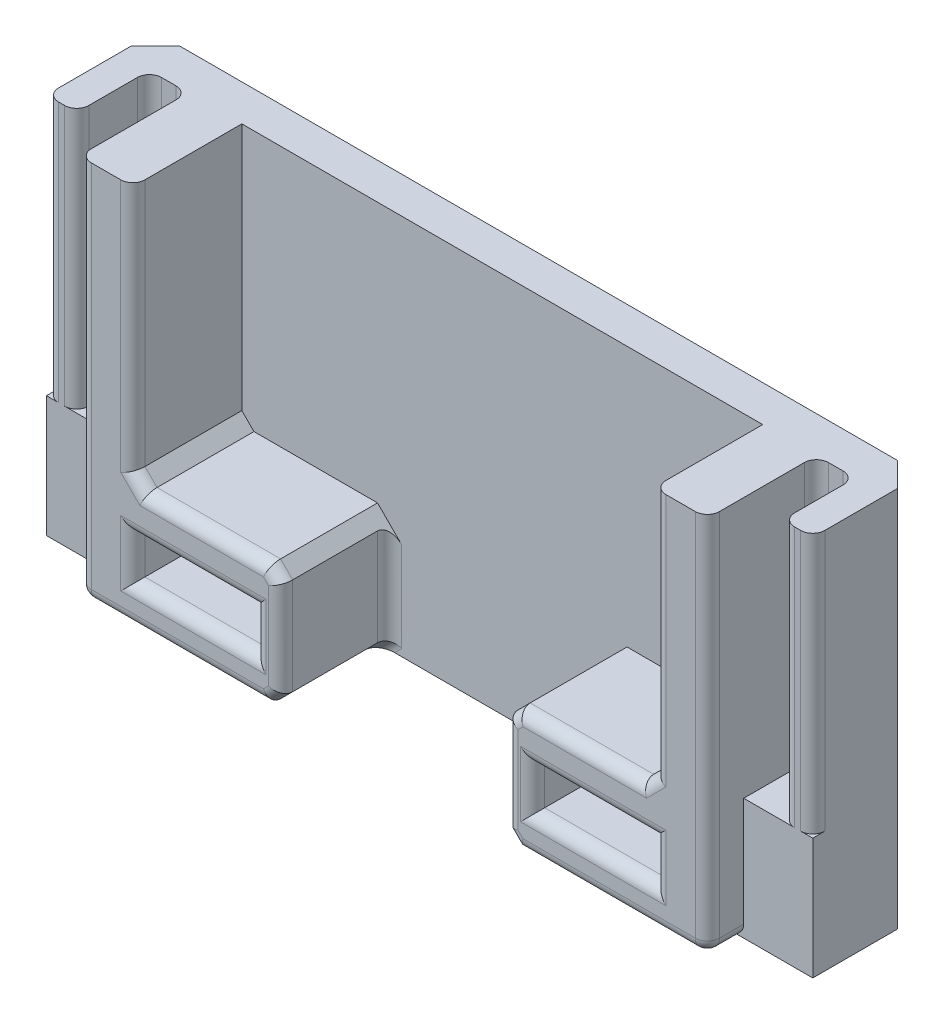
SolidWorks part; units mm, degrees
ref_plane "Plan de face" through (0, 0, 0) normal (0, 0, 1) x (1, 0, 0)
ref_plane "Plan de dessus" through (0, 0, 0) normal (0, 1, 0) x (1, 0, 0)
ref_plane "Plan de droite" through (0, 0, 0) normal (1, 0, 0) x (0, 0, -1)
sketch "Esquisse2" plane through (0, 0, 0) normal (0, 0, 1) x (1, 0, 0)
  line L0 (0, -21.5) -> (0, -31.5)
  line L1 (-21.5, -21.5) -> (21.5, -21.5)
  line L2 (-21.5, -21.5) -> (-21.5, 21.5)
  line L3 (-21.5, 21.5) -> (21.5, 21.5)
  line L4 (21.5, -21.5) -> (21.5, 21.5)
  line L5 (-21.5, -21.5) -> (21.5, 21.5) construction
  line L6 (-21.5, 21.5) -> (21.5, -21.5) construction
  line L7 (-25.9306, -31.5) -> (25.9306, -31.5)
  line L8 (-25.9306, -31.5) -> (-25.9306, 31.5)
  line L9 (-25.9306, 31.5) -> (25.9306, 31.5)
  line L10 (25.9306, -31.5) -> (25.9306, 31.5)
  line L11 (-25.9306, -31.5) -> (25.9306, 31.5) construction
  line L12 (-25.9306, 31.5) -> (25.9306, -31.5) construction
  line L13 (9.3, -21.5) -> (9.3, -31.5)
  line L14 (9.3, -21.5) -> (-9.3, -21.5)
  line L15 (0, -21.5) -> (0, -31.5)
  line L16 (9.3, -31.5) -> (-9.3, -31.5)
  line L17 (-9.3, -21.5) -> (-9.3, -31.5)
  point P0 (0, 0)
  point P6 (0, 0)
  dimension "D1" = 43
  dimension "D2" = 43
  dimension "D3" = 10
  dimension "D4" = 9.3
extrude "Boss.-Extru.2" add sketch "Esquisse2" along normal blind 9 contours L17 L1 L2 L3 L4 L13 L7 L10 L9 L8 region at (-10.116, -26.5, 0)
sketch "Esquisse3" plane through (0, 0, 0) normal (0, 0, -1) x (-1, 0, 0)
  line L1 (-25.9306, 31.5) -> (25.9306, 31.5)
  line L2 (-25.9306, 31.5) -> (-25.9306, -31.5)
  line L3 (-25.9306, -31.5) -> (25.9306, -31.5)
  line L4 (25.9306, 31.5) -> (25.9306, -31.5)
extrude "Boss.-Extru.3" add sketch "Esquisse3" along normal blind 3
sketch "Esquisse4" plane through (0, 0, 9) normal (0, 0, 1) x (1, 0, 0)
  line L0 (0, 31.5) -> (0, -31.5)
  line L1 (-25.9306, 31.5) -> (25.9306, 31.5) construction
  line L2 (9.3, -31.5) -> (-9.3, -31.5) construction
  line L3 (-21.5, 21.5) -> (-21.5, 28.3955)
  line L4 (-25.9306, 0) -> (0, 0)
  line L5 (-21.5, 28.3955) -> (-11.5, 28.3955)
  line L6 (-21.5, 28.3955) -> (-21.5, 24.9955)
  line L7 (-21.5, 24.9955) -> (-11.5, 24.9955)
  line L8 (-11.5, 28.3955) -> (-11.5, 24.9955)
  line L9 (-25.9306, -31.5) -> (-25.9306, 31.5) construction
  line L10 (-21.5, -24.9955) -> (-11.5, -24.9955)
  line L11 (-11.5, -28.3955) -> (-11.5, -24.9955)
  line L12 (-21.5, -28.3955) -> (-11.5, -28.3955)
  line L13 (-21.5, -28.3955) -> (-21.5, -24.9955)
  line L14 (21.5, -28.3955) -> (21.5, -24.9955)
  line L15 (21.5, -28.3955) -> (11.5, -28.3955)
  line L16 (11.5, -28.3955) -> (11.5, -24.9955)
  line L17 (21.5, -24.9955) -> (11.5, -24.9955)
  line L18 (21.5, 24.9955) -> (11.5, 24.9955)
  line L19 (11.5, 28.3955) -> (11.5, 24.9955)
  line L20 (21.5, 28.3955) -> (11.5, 28.3955)
  line L21 (21.5, 28.3955) -> (21.5, 24.9955)
  dimension "D1" = 3.4
extrude "Enlèv. mat.-Extru.1" cut sketch "Esquisse4" against normal blind 7 contours L13 L12 L11 L10 | L14 L17 L16 L15 | L18 L19 L20 L21 | L6 L7 L8 L5 region at (-16.5, -26.6955, 9) region at (16.5, -26.6955, 9)
sketch "Esquisse5" plane through (0, 31.5, 0) normal (0, 1, 0) x (1, 0, 0)
  line L0 (0, 3) -> (0, -9)
  line L1 (-25.9306, 3) -> (25.9306, 3) construction
  line L2 (-25.9306, -9) -> (25.9306, -9) construction
  line L3 (25.9306, 0) -> (29.1306, 0)
  line L4 (-25.9306, 3) -> (-29.1306, 3)
  line L5 (-25.9306, 3) -> (-25.9306, 0)
  line L6 (-25.9306, 0) -> (-29.1306, 0)
  line L7 (-29.1306, 3) -> (-29.1306, 0)
  line L8 (-29.1306, 3) -> (-31.6306, 3)
  line L9 (-29.1306, 3) -> (-29.1306, -6)
  line L10 (-29.1306, -6) -> (-31.6306, -6)
  line L11 (-31.6306, 3) -> (-31.6306, -6)
  line L12 (29.1306, 3) -> (29.1306, 0)
  line L13 (25.9306, 3) -> (29.1306, 3)
  line L14 (25.9306, 3) -> (25.9306, 0)
  line L15 (29.1306, -6) -> (31.6306, -6)
  line L16 (31.6306, 3) -> (31.6306, -6)
  line L17 (29.1306, 3) -> (31.6306, 3)
  line L18 (29.1306, 3) -> (29.1306, -6)
  line M10 (25.9306, -9) -> (25.9306, 3)
  line M12 (-25.9306, 3) -> (-25.9306, -9)
  dimension "D1" = 9
  dimension "D2" = 2.5
  dimension "D3" = 3.2
extrude "Boss.-Extru.4" add sketch "Esquisse5" against normal up to surface (63 mm away) contours L8 L11 L10 L9 L7 | L4 L7 L6 M12 | L13 L3 L12 M10 | L12 L18 L15 L16 L17 region at (27.5306, 31.5, -1.5) region at (30.3806, 31.5, 1.5) region at (-27.5306, 31.5, -1.5) region at (-30.3806, 31.5, 1.5) up to face at (0, -31.5, 3.75)
chamfer "Chanfrein1" distance 1 angle 45 4 edges at (-21.5, -21.5, 4.5) (21.5, -21.5, 4.5) (21.5, 21.5, 4.5) (-21.5, 21.5, 4.5)
chamfer "Chanfrein2" distance 2 angle 45 4 edges at (-31.6306, 0, -3) (0, -31.5, -3) (31.6306, 0, -3) (0, 31.5, -3)
fillet "Congé1" radius 1 8 edges at (31.6306, 0, 6) (29.1306, 0, 6) (29.1306, 0, 0) (25.9306, 0, 0) (-29.1306, 0, 6) (-31.6306, 0, 6) (-29.1306, 0, 0) (-25.9306, 0, 0)
fillet "Congé2" radius 1 36 edges at (-31.6306, 31.5, 2) (-31.3377, 31.5, 5.7071) (-30.3806, 31.5, 6) (-29.4235, 31.5, 5.7071) (-29.1306, 31.5, 3) (-28.8377, 31.5, 0.2929) (-27.5306, 31.5, 0) (-26.2235, 31.5, 0.2929) (-31.6306, -31.5, 2) (-31.3377, -31.5, 5.7071) (-30.3806, -31.5, 6) (-29.4235, -31.5, 5.7071) (-29.1306, -31.5, 3) (-28.8377, -31.5, 0.2929) (-27.5306, -31.5, 0) (-26.2235, -31.5, 0.2929) (31.6306, -31.5, 2) (31.3377, -31.5, 5.7071) (30.3806, -31.5, 6) (29.4235, -31.5, 5.7071) (29.1306, -31.5, 3) (28.8377, -31.5, 0.2929) (27.5306, -31.5, 0) (26.2235, -31.5, 0.2929) (31.6306, 31.5, 2) (31.3377, 31.5, 5.7071) (30.3806, 31.5, 6) (29.4235, 31.5, 5.7071) (29.1306, 31.5, 3) (28.8377, 31.5, 0.2929) (27.5306, 31.5, 0) (26.2235, 31.5, 0.2929) (-25.9306, 31.5, 5) (-25.9306, -31.5, 5) (25.9306, -31.5, 5) (25.9306, 31.5, 5)
chamfer "Chanfrein4" distance 1 angle 45 4 edges at (9.3, -31.5, 4.5) (-9.3, -31.5, 4.5) (9.3, -21.5, 4.5) (-9.3, -21.5, 4.5)
fillet "Congé4" radius 1 40 edges at (-16.5, 24.9955, 9) (-11.5, 26.6955, 9) (-16.5, 28.3955, 9) (-21.5, 26.6955, 9) (11.5, 26.6955, 9) (16.5, 24.9955, 9) (21.5, 26.6955, 9) (16.5, 28.3955, 9) (-11.5, -26.6955, 9) (-16.5, -24.9955, 9) (-21.5, -26.6955, 9) (-16.5, -28.3955, 9) (9.8, -22, 9) (15.4, -21.5, 9) (21, -21, 9) (21.5, 0, 9) (21, 21, 9) (0, 21.5, 9) (-21, 21, 9) (-21.5, 0, 9) (-21, -21, 9) (-15.4, -21.5, 9) (-9.8, -22, 9) (-9.3, -26.5, 9) (-9.8, -31, 9) (-17.6153, -31.5, 9) (-25.6377, -31.2071, 9) (-25.9306, 0, 9) (-25.6377, 31.2071, 9) (0, 31.5, 9) (25.6377, 31.2071, 9) (25.9306, 0, 9) (25.6377, -31.2071, 9) (17.6153, -31.5, 9) (9.8, -31, 9) (9.3, -26.5, 9) (16.5, -24.9955, 9) (11.5, -26.6955, 9) (16.5, -28.3955, 9) (21.5, -26.6955, 9)
fillet "Congé5" radius 1 4 edges at (9.8, -31, 0) (9.3, -26.5, 0) (-9.8, -31, 0) (-9.3, -26.5, 0)
sketch "Esquisse6" plane through (0, -31.5, 0) normal (0, -1, 0) x (1, 0, 0)
  line L0 (-26.9306, -1) -> (26.9306, -1) construction
  line L1 (31.6306, 5) -> (24.9271, 5)
  line L2 (31.6306, 5) -> (31.6306, -1)
  line L3 (31.6306, -1) -> (24.9271, -1)
  line L4 (24.9271, 5) -> (24.9271, -1)
  line L5 (0, -1) -> (0, 5)
  line L6 (24.9271, 5) -> (31.6306, 5)
  line L7 (24.9271, 5) -> (24.9271, 6)
  line L8 (24.9271, 6) -> (31.6306, 6)
  line L9 (31.6306, 5) -> (31.6306, 6)
  line L10 (-24.9271, 6) -> (-31.6306, 6)
  line L11 (-31.6306, 5) -> (-31.6306, 6)
  line L12 (-24.9271, 5) -> (-31.6306, 5)
  line L13 (-24.9271, 5) -> (-24.9271, 6)
  line L14 (-31.6306, -1) -> (-24.9271, -1)
  line L15 (-24.9271, 5) -> (-24.9271, -1)
  line L16 (-31.6306, 5) -> (-24.9271, 5)
  line L17 (-31.6306, 5) -> (-31.6306, -1)
  line M14 (-24.9306, 8) -> (-24.9306, 1)
  arc M15 (-24.9306, 1) -> (-26.9306, -1) centre (-26.9306, 1) cw
  arc M17 (26.9306, -1) -> (24.9306, 1) centre (26.9306, 1) cw
  line M18 (24.9306, 1) -> (24.9306, 8)
extrude "Boss.-Extru.5" add sketch "Esquisse6" against normal blind 10 contours L12 L17 L14 M15 M14 | L12 L10 L11 M14 | L3 L2 L1 M18 M17 | L1 L9 L8 M18 region at (28.344, -31.5, 2.0557) region at (28.2806, -31.5, 5.5) region at (-28.2806, -31.5, 5.5) region at (-28.344, -31.5, 2.0557)
sketch "Esquisse7" plane through (31.6306, 0, 0) normal (1, 0, 0) x (0, 0, -1)
  line L0 (-9, -30.5) -> (-9, 30.5) construction
  line L1 (-9, 0) -> (16.2814, 0)
  line L2 (-9, 0) -> (-9, 35.176)
  line L3 (-9, 35.176) -> (16.2814, 35.176)
  line L4 (16.2814, 0) -> (16.2814, 35.176)
extrude "Enlèv. mat.-Extru.2" cut sketch "Esquisse7" against normal blind 79
